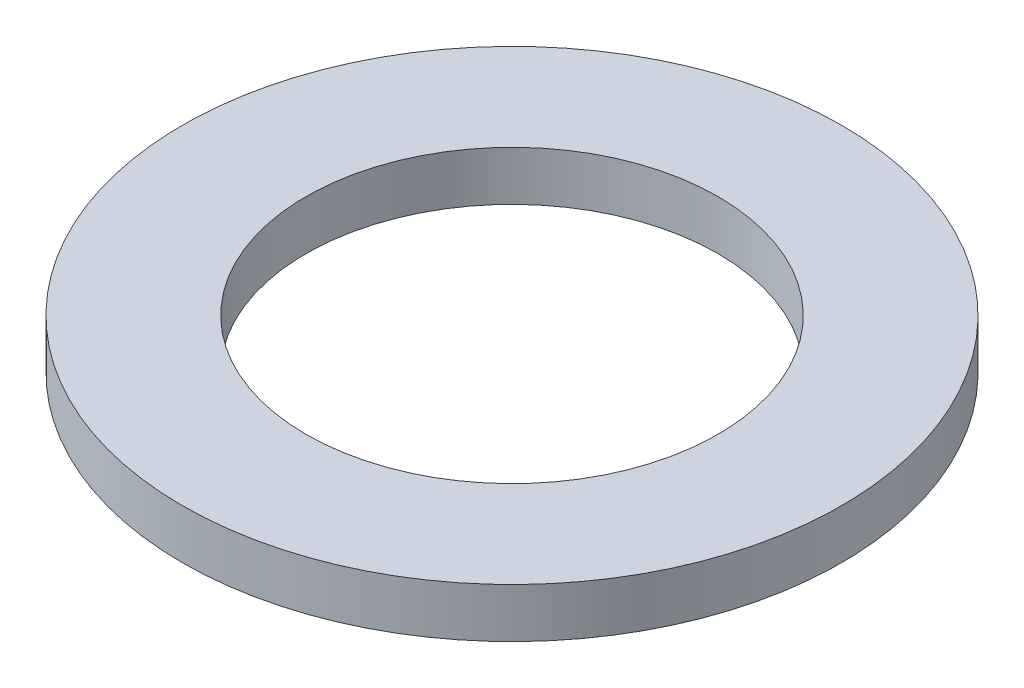
SolidWorks part; units mm, degrees
ref_plane "Front Plane" through (0, 0, 0) normal (0, 0, 1) x (1, 0, 0)
ref_plane "Top Plane" through (0, 0, 0) normal (0, 1, 0) x (1, 0, 0)
ref_plane "Right Plane" through (0, 0, 0) normal (1, 0, 0) x (0, 0, -1)
sketch "Sketch1" plane through (0, 0, 0) normal (0, 1, 0) x (1, 0, 0)
  circle A0 centre (0, 0) radius 60
  dimension "FLANGE_OD" = 120
extrude "Boss-Extrude1" add sketch "Sketch1" along normal blind 9
sketch "Sketch2" plane through (0, 0, 0) normal (0, 1, 0) x (1, 0, 0)
  circle A0 centre (0, 0) radius 37.5
  dimension "BORE_D" = 75
extrude "Cut-Extrude1" cut sketch "Sketch2" along normal through all
sketch "Sketch3" plane through (0, 9, 0) normal (0, 1, 0) x (1, 0, 0)
  circle A0 centre (0, 0) radius 22.3142 construction
  circle A1 centre (-22.3142, 0) radius 2.4534
  dimension "BOLT_D" = 4.9068
  dimension "BOLT_PCD" = 44.6284
extrude "Cut-Extrude2" cut sketch "Sketch3" against normal blind 5.9233 rebuild error yes
pattern_circular "CirPattern1" count 5 over 360 rebuild error yes
